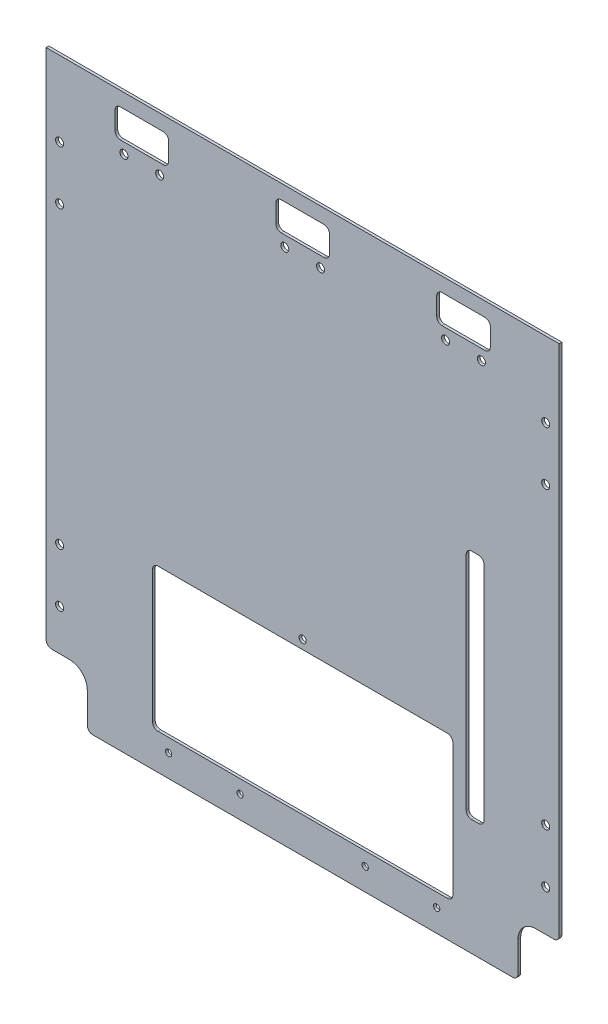
SolidWorks part; units mm, degrees
material "1023 Tôle d'acier au carbone (SS)"
ref_plane "Front" through (0, 0, 0) normal (0, 0, 1) x (1, 0, 0)
ref_plane "Top" through (0, 0, 0) normal (0, 1, 0) x (1, 0, 0)
ref_plane "Right" through (0, 0, 0) normal (1, 0, 0) x (0, 0, -1)
sketch "Esquisse1" plane through (0, 0, 0) normal (0, 0, 1) x (1, 0, 0)
  line L1 (0, 0) -> (287, 0)
  line L2 (0, 0) -> (0, 320)
  line L3 (0, 320) -> (287, 320)
  line L4 (287, 0) -> (287, 320)
  dimension "D1" = 287
  dimension "D2" = 320
extrude "Boss.-Extru.1" add sketch "Esquisse1" along normal blind 1.5
sketch "Esquisse2" plane through (0, 0, 1.5) normal (0, 0, 1) x (1, 0, 0)
  line L0 (143.5, 0) -> (143.5, 172.6222) construction
  line L1 (287, 0) -> (264, 0)
  line L2 (287, 0) -> (287, 30)
  line L3 (287, 30) -> (264, 30)
  line L4 (264, 0) -> (264, 30)
  line L5 (0, 0) -> (287, 0) construction
  line L6 (23, 0) -> (23, 30)
  line L7 (0, 30) -> (23, 30)
  line L8 (0, 0) -> (0, 30)
  line L9 (0, 0) -> (23, 0)
  dimension "D1" = 23
  dimension "D2" = 30
extrude "Enlèv. mat.-Extru.1" cut sketch "Esquisse2" against normal through all both and the other way through all
fillet "Congé1" radius 10 2 edges at (23, 30, 0.75) (264, 30, 0.75)
fillet "Congé2" radius 3 4 edges at (264, 0, 0.75) (287, 30, 0.75) (23, 0, 0.75) (0, 30, 0.75)
sketch "Esquisse3" plane through (0, 0, 1.5) normal (0, 0, 1) x (1, 0, 0)
  line L0 (26, 0) -> (261, 0) construction
  line L1 (235, 195) -> (245, 195)
  line L2 (235, 195) -> (235, 65)
  line L3 (235, 65) -> (245, 65)
  line L4 (245, 195) -> (245, 65)
  dimension "D1" = 10
  dimension "D2" = 235
  dimension "D3" = 65
  dimension "D4" = 130
extrude "Enlèv. mat.-Extru.2" cut sketch "Esquisse3" against normal through all both and the other way through all
sketch "Esquisse4" plane through (0, 0, 1.5) normal (0, 0, 1) x (1, 0, 0)
  line L0 (26, 0) -> (261, 0) construction
  line L1 (59.5, 20) -> (227.5, 20)
  line L2 (59.5, 20) -> (59.5, 100)
  line L3 (59.5, 100) -> (227.5, 100)
  line L4 (227.5, 20) -> (227.5, 100)
  line L5 (143.5, 20) -> (143.5, 0) construction
  dimension "D1" = 80
  dimension "D2" = 20
  dimension "D3" = 168
extrude "Enlèv. mat.-Extru.3" cut sketch "Esquisse4" against normal through all both and the other way through all
fillet "Congé3" radius 3 8 edges at (235, 195, 0.75) (245, 195, 0.75) (245, 65, 0.75) (235, 65, 0.75) (227.5, 20, 0.75) (227.5, 100, 0.75) (59.5, 100, 0.75) (59.5, 20, 0.75)
sketch "Esquisse5" plane through (0, 0, 1.5) normal (0, 0, 1) x (1, 0, 0)
  line L0 (143.5, 0) -> (143.5, 105) construction
  line L1 (26, 0) -> (261, 0) construction
  line L2 (143.5, 12.5) -> (68.5, 12.5) construction
  line L3 (224.5, 20) -> (62.5, 20) construction
  circle A0 centre (143.5, 105) radius 2
  circle A1 centre (68.5, 12.5) radius 1.75
  circle A2 centre (108.5, 12.5) radius 1.75
  circle A3 centre (178.5, 12.5) radius 1.75
  circle A4 centre (218.5, 12.5) radius 1.75
  dimension "D1" = 4
  dimension "D3" = 150
  dimension "D4" = 3.5
  dimension "D6" = 40
  dimension "D2" = 105
  dimension "D5" = 7.5
extrude "Enlèv. mat.-Extru.4" cut sketch "Esquisse5" against normal through all both and the other way through all
sketch "Esquisse6" plane through (0, 0, 1.5) normal (0, 0, 1) x (1, 0, 0)
  line L0 (279.5, 308.1366) -> (279.5, -83.1051) construction
  line L1 (43.5, 290) -> (63.5, 290) construction
  line L2 (143.5, 0) -> (143.5, 67.282) construction
  line L3 (26, 0) -> (261, 0) construction
  line L4 (279.5, 165.5) -> (143.5, 165.5) construction
  line L5 (143.5, 320) -> (143.5, 263.6078) construction
  line L6 (287, 320) -> (0, 320) construction
  line L7 (243.5, 290) -> (223.5, 290) construction
  circle A0 centre (279.5, 83) radius 2.25
  circle A1 centre (279.5, 53) radius 2.25
  circle A2 centre (279.5, 278) radius 2.25
  circle A3 centre (279.5, 248) radius 2.25
  circle A4 centre (7.5, 248) radius 2.25
  circle A5 centre (7.5, 278) radius 2.25
  circle A6 centre (7.5, 53) radius 2.25
  circle A7 centre (7.5, 83) radius 2.25
  circle A8 centre (133.5, 290) radius 2.25
  circle A9 centre (153.5, 290) radius 2.25
  circle A10 centre (43.5, 290) radius 2.25
  circle A11 centre (63.5, 290) radius 2.25
  circle A12 centre (223.5, 290) radius 2.25
  circle A13 centre (243.5, 290) radius 2.25
  point P36 (53.5, 290)
  dimension "D2" = 4.5
  dimension "D3" = 30
  dimension "D4" = 53
  dimension "D5" = 195
  dimension "D8" = 20
  dimension "D1" = 136
  dimension "D6" = 20
  dimension "D7" = 30
  dimension "D9" = 90
  dimension "D10" = 30
extrude "Enlèv. mat.-Extru.5" cut sketch "Esquisse6" against normal through all both and the other way through all
sketch "Esquisse7" plane through (0, 0, 1.5) normal (0, 0, 1) x (1, 0, 0)
  line L0 (133.5, 290) -> (153.5, 290) construction
  line L1 (143.5, 290) -> (143.5, 312) construction
  line L2 (158.5, 312) -> (128.5, 312)
  line L3 (128.5, 312) -> (128.5, 296)
  line L4 (128.5, 296) -> (158.5, 296)
  line L5 (158.5, 312) -> (158.5, 296)
  line L6 (43.5, 290) -> (63.5, 290) construction
  line L7 (53.5, 290) -> (53.5, 312) construction
  line L8 (68.5, 312) -> (38.5, 312)
  line L9 (38.5, 312) -> (38.5, 296)
  line L10 (38.5, 296) -> (68.5, 296)
  line L11 (68.5, 312) -> (68.5, 296)
  line L12 (233.5, 290) -> (233.5, 312) construction
  line L13 (243.5, 290) -> (223.5, 290) construction
  line L14 (218.5, 312) -> (218.5, 296)
  line L15 (248.5, 296) -> (218.5, 296)
  line L16 (248.5, 312) -> (248.5, 296)
  line L17 (218.5, 312) -> (248.5, 312)
  point P10 (143.5, 296)
  point P21 (53.5, 296)
  point P30 (233.5, 296)
  dimension "D1" = 22
  dimension "D2" = 16
  dimension "D3" = 30
  dimension "D4" = 30
  dimension "D5" = 22
  dimension "D6" = 16
extrude "Enlèv. mat.-Extru.6" cut sketch "Esquisse7" against normal through all both and the other way through all
fillet "Congé4" radius 3 12 edges at (218.5, 296, 0.75) (248.5, 296, 0.75) (248.5, 312, 0.75) (218.5, 312, 0.75) (128.5, 312, 0.75) (158.5, 312, 0.75) (128.5, 296, 0.75) (158.5, 296, 0.75) (68.5, 296, 0.75) (68.5, 312, 0.75) (38.5, 312, 0.75) (38.5, 296, 0.75)
